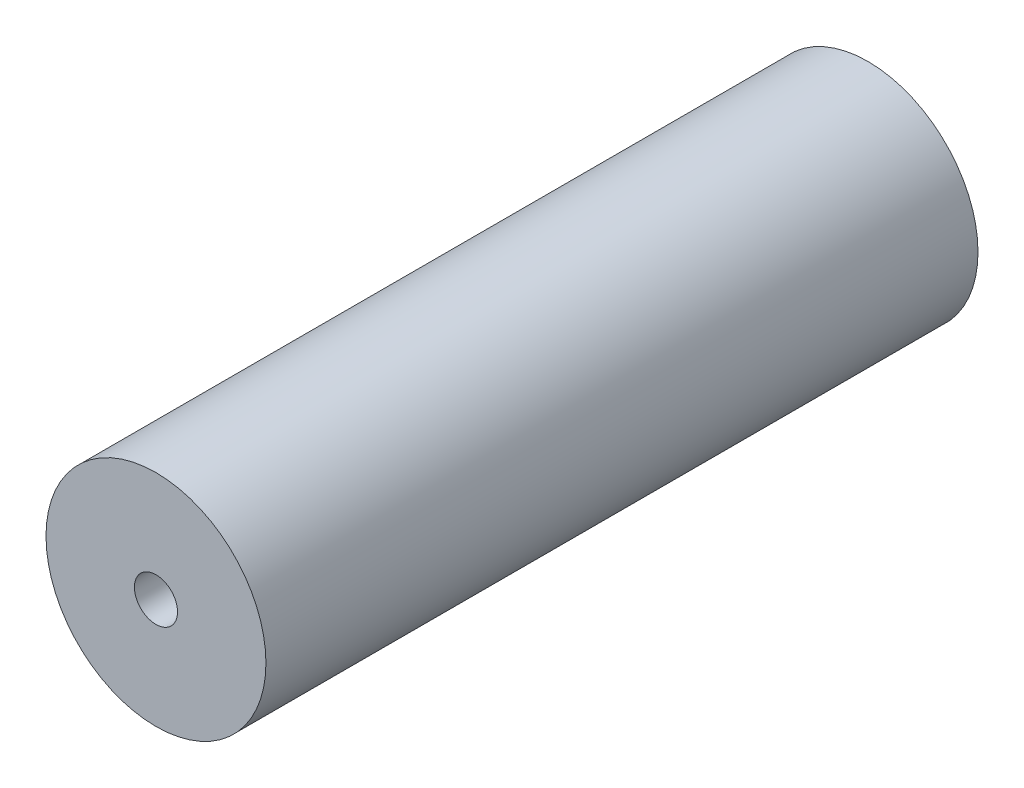
SolidWorks part; units mm, degrees
ref_plane "Front Plane" through (0, 0, 0) normal (0, 0, 1) x (1, 0, 0)
ref_plane "Top Plane" through (0, 0, 0) normal (0, 1, 0) x (1, 0, 0)
ref_plane "Right Plane" through (0, 0, 0) normal (1, 0, 0) x (0, 0, -1)
sketch "Sketch1" plane through (0, 0, 0) normal (0, 0, 1) x (1, 0, 0)
  circle A0 centre (0, 0) radius 12.7
  circle A1 centre (0, 0) radius 2.4892
  dimension "D1" = 25.4
  dimension "D2" = 4.9784
extrude "Boss-Extrude1" add sketch "Sketch1" along normal blind 82.2325
